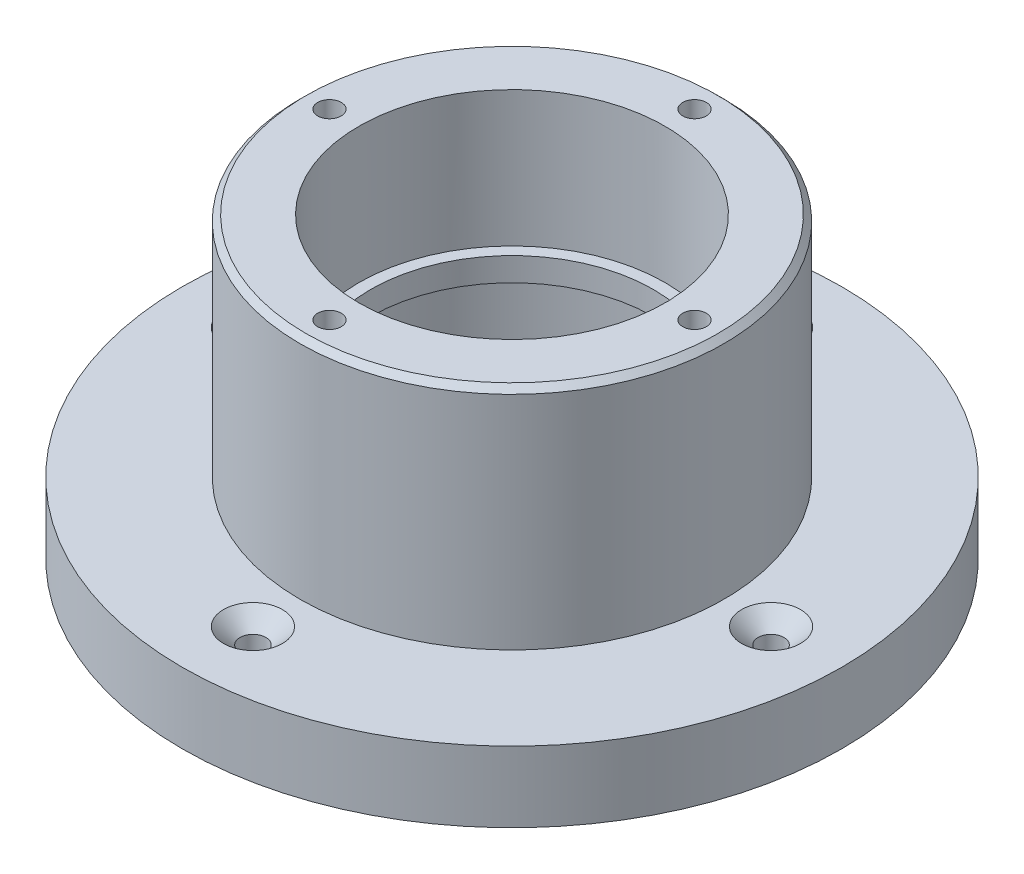
SolidWorks part; units mm, degrees
material "ABS"
ref_plane "Спереди" through (0, 0, 0) normal (0, 0, 1) x (1, 0, 0)
ref_plane "Сверху" through (0, 0, 0) normal (0, 1, 0) x (1, 0, 0)
ref_plane "Справа" through (0, 0, 0) normal (1, 0, 0) x (0, 0, -1)
sketch "Эскиз1" plane through (0, 0, 0) normal (0, 1, 0) x (1, 0, 0)
  circle A0 centre (0, 0) radius 26
  dimension "D1" = 52
extrude "Бобышка-Вытянуть1" add sketch "Эскиз1" along normal blind 4
sketch "Эскиз2" plane through (0, 4, 0) normal (0, 1, 0) x (1, 0, 0)
  circle A0 centre (0, 0) radius 18
  dimension "D1" = 36
extrude "Бобышка-Вытянуть2" add sketch "Эскиз2" along normal blind 19.3
sketch "Эскиз3" plane through (0, 23.3, 0) normal (0, 1, 0) x (1, 0, 0)
  circle A0 centre (0, 0) radius 13
  dimension "D1" = 26
extrude "Вырез-Вытянуть1" cut sketch "Эскиз3" along direction (0, 1, 0) on the side against the normal offset from surface (10.3 mm away) 13 up to face at (0, 0, 26)
sketch "Эскиз4" plane through (0, 4, 0) normal (0, 1, 0) x (1, 0, 0)
  circle A0 centre (0, 0) radius 22 construction
  circle A1 centre (-22, 0) radius 2.2
  circle A2 centre (0, 22) radius 2.2
  circle A3 centre (22, 0) radius 2.2
  circle A4 centre (0, -22) radius 2.2
  point P14 (0, 0)
  dimension "D1" = 44
  dimension "D2" = 4.4
  dimension "D3" = 4
sketch "Эскиз6" plane through (0, 13, 0) normal (0, 1, 0) x (1, 0, 0)
  circle A0 centre (0, 0) radius 13
  dimension "D1" = 26
extrude "Вырез-Вытянуть4" cut sketch "Эскиз6" against normal through all
sketch "Эскиз7" plane through (0, 23.3, 0) normal (0, 1, 0) x (1, 0, 0)
  circle A0 centre (0, 0) radius 15.5 construction
  circle A1 centre (-15.5, 0) radius 1
  circle A2 centre (0, 15.5) radius 1
  circle A3 centre (15.5, 0) radius 1
  circle A4 centre (0, -15.5) radius 1
  point P14 (0, 0)
  dimension "D1" = 31
  dimension "D2" = 2
extrude "Вырез-Вытянуть5" cut sketch "Эскиз7" against normal blind 5
sketch "Эскиз8" plane through (0, 4, 0) normal (0, 1, 0) x (1, 0, 0)
  circle A0 centre (0, 0) radius 26
  circle A1 centre (0, 0) radius 28
  dimension "D1" = 56
  dimension "D2" = 52
extrude "Бобышка-Вытянуть3" add sketch "Эскиз8" against normal blind 6
chamfer "Фаска1" distance 0.5 angle 45 1 edges at (0, -2, 26)
chamfer "Фаска2" distance 0.5 angle 45 1 edges at (0, 23.3, 18)
ref_axis "Ось1" through (0, -20.7688, 22) along (0, 1, 0)
sketch "Эскиз9" plane through (0, 0, 0) normal (1, 0, 0) x (0, 0, -1)
  line L1 (-22, -20.7688) -> (-22, 30.1347) construction
  line L2 (-20.9, 2.648) -> (-19.5, 4)
  line L3 (22, 4) -> (-22, 4) construction
  line L4 (-19.5, 4) -> (-22, 4)
  line L5 (-19.8, 4) -> (-24.2, 4) construction
  line L6 (-22, 2.648) -> (-22, 4)
  line L7 (-20.9, 2.648) -> (-20.9, -2)
  line L8 (-28, -2) -> (28, -2) construction
  line L9 (-20.9, -2) -> (-22, -2)
  line L10 (-22, -2) -> (-22, 2.648)
  dimension "D1" = 1.1
  dimension "D2" = 2.5
  dimension "D3" = 46
revolve "Вырез-Повернуть2" cut sketch "Эскиз9" angle 360 about axis through (0, -20.7688, 22) along (0, 1, 0)
pattern_circular "Круговой массив1" count 4 over 360 about axis through (0, 23.3, 0) along (0, -1, 0) of "Вырез-Повернуть2"
sketch "Эскиз10" plane through (0, 0, 0) normal (0, -1, 0) x (1, 0, 0)
  circle A0 centre (0, 0) radius 15
  dimension "D1" = 30
extrude "Вырез-Вытянуть7" cut sketch "Эскиз10" against normal blind 11.8 contours A0
sketch "Эскиз11" plane through (0, 11.8, 0) normal (0, -1, 0) x (1, 0, 0)
  circle A2 centre (0, 0) radius 15
  circle A3 centre (0, 0) radius 12
  dimension "D1" = 24
extrude "Бобышка-Вытянуть4" add sketch "Эскиз11" along normal blind 2
